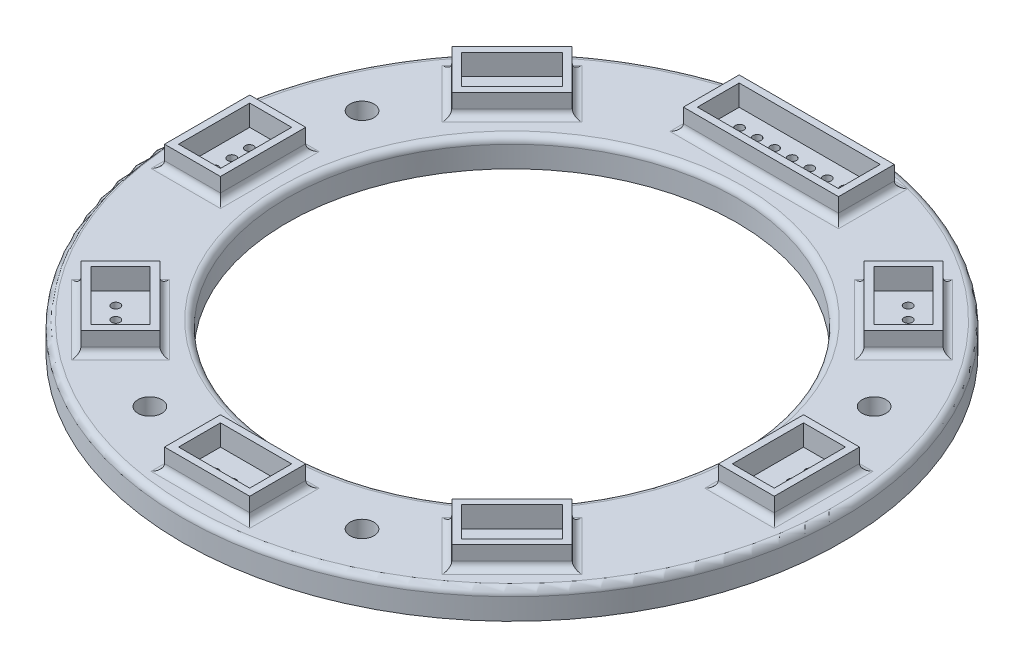
SolidWorks part; units mm, degrees
ref_plane "Front Plane" through (0, 0, 0) normal (0, 0, 1) x (1, 0, 0)
ref_plane "Top Plane" through (0, 0, 0) normal (0, 1, 0) x (1, 0, 0)
ref_plane "Right Plane" through (0, 0, 0) normal (1, 0, 0) x (0, 0, -1)
sketch "Sketch1" plane through (0, 0, 0) normal (0, 1, 0) x (1, 0, 0)
  circle A0 centre (0, 0) radius 32.05
  circle A1 centre (0, 0) radius 47
  dimension "D1" = 64.1
  dimension "D2" = 94
extrude "Boss-Extrude1" add sketch "Sketch1" along normal blind 1
sketch "Sketch2" plane through (0, 0, 0) normal (0, -1, 0) x (1, 0, 0)
  circle A0 centre (0, 0) radius 33.05
  circle A1 centre (0, 0) radius 46
  circle A2 centre (0, 0) radius 32.05 construction
  circle A3 centre (0, 0) radius 47 construction
  circle A4 centre (0, 0) radius 32.05
  circle A5 centre (0, 0) radius 47
  circle M4 centre (0, 0) radius 47
  circle M5 centre (0, 0) radius 32.05
  dimension "D1" = 1
  dimension "D2" = 1
extrude "Boss-Extrude2" add sketch "Sketch2" along normal blind 3 contours A1 M4 | A0 M5 region at (-32.1152, 0, 0) region at (-46.8671, 0, 0)
sketch "Sketch4" plane through (0, 1, 0) normal (0, 1, 0) x (1, 0, 0)
  line L0 (33.485, 26.4493) -> (26.4493, 33.485)
  line L1 (26.4493, 33.485) -> (22.3623, 29.398)
  line L2 (22.3623, 29.398) -> (29.398, 22.3623)
  line L3 (29.398, 22.3623) -> (33.485, 26.4493)
  line L4 (33.6265, 26.4493) -> (26.4493, 33.6265)
  line L5 (26.4493, 33.6265) -> (22.2208, 29.398)
  line L6 (22.2208, 29.398) -> (29.398, 22.2208)
  line L7 (29.398, 22.2208) -> (33.6265, 26.4493)
  line L8 (26.4493, 35.0407) -> (20.8066, 29.398)
  line L9 (20.8066, 29.398) -> (29.398, 20.8066)
  line L10 (29.398, 20.8066) -> (35.0407, 26.4493)
  line L11 (35.0407, 26.4493) -> (26.4493, 35.0407)
  line L12 (0, 0) -> (25.1023, 25.1023) construction
  line L13 (0, 0) -> (0, 27.9664) construction
  dimension "D3" = 36.6
  dimension "D4" = 9.95
  dimension "D5" = 5.78
  dimension "D6" = 45
  dimension "D1" = 0.1
  dimension "D2" = 1
extrude "Boss-Extrude3" add sketch "Sketch4" along normal blind 3 contours L10 L11 L8 L9 L7 L6 L5 L4 region at (30.6027, 1, -30.6027)
sketch "Sketch7" plane through (0, 1, 0) normal (0, 1, 0) x (1, 0, 0)
  line L0 (-30.4712, 26.4831) -> (-29.5661, 26.4831) construction
  line L1 (-28.7034, 28.2509) -> (-27.7983, 28.2509) construction
  line L2 (-26.9357, 30.0187) -> (-26.0306, 30.0187) construction
  circle A0 centre (-30.0187, 26.4831) radius 0.6
  circle A1 centre (-28.2509, 28.2509) radius 0.6
  circle A2 centre (-26.4831, 30.0187) radius 0.6
  dimension "D1" = 1.2
extrude "Cut-Extrude2" cut sketch "Sketch7" against normal up to next
pattern_circular "CirPattern4" count 8 over 360 about axis through (0, 1, 0) along (0, -1, 0) skipping 7 of "Boss-Extrude3"
sketch "Sketch5" plane through (0, 1, 0) normal (0, 1, 0) x (1, 0, 0)
  line L25 (-10.06, 36.5) -> (-10.06, 42.46)
  line L26 (-9.96, 36.6) -> (9.96, 36.6)
  line L27 (-9.96, 36.6) -> (-9.96, 42.36)
  line L28 (-9.96, 42.36) -> (9.96, 42.36)
  line L29 (9.96, 36.6) -> (9.96, 42.36)
  line L30 (-10.06, 42.46) -> (10.06, 42.46)
  line L31 (10.06, 36.5) -> (10.06, 42.46)
  line L32 (-10.06, 36.5) -> (10.06, 36.5)
  line L33 (-11.06, 35.5) -> (11.06, 35.5)
  line L34 (11.06, 35.5) -> (11.06, 43.46)
  line L35 (-11.06, 43.46) -> (11.06, 43.46)
  line L36 (-11.06, 35.5) -> (-11.06, 43.46)
  point P0 (0, 43.46)
  dimension "D1" = 36.6
  dimension "D2" = 5.76
  dimension "D5" = 19.92
  dimension "D3" = 0.1
  dimension "D4" = 1
extrude "Boss-Extrude4" add sketch "Sketch5" along normal blind 3 contours L36 L33 L34 L35 L32 L25 L30 L31 region at (-10.8249, 1, -39.48)
fillet "Fillet2" radius 0.96 34 edges at (-32.2193, 1, -23.628) (-25.1023, 1, -25.1023) (-23.628, 1, -32.2193) (-30.745, 1, -30.745) (-39.49, 1, 6.075) (-35.5, 1, 0) (-39.49, 1, -6.075) (-43.48, 1, 0) (-23.628, 1, 32.2193) (-25.1023, 1, 25.1023) (-32.2193, 1, 23.628) (-30.745, 1, 30.745) (6.075, 1, 39.49) (0, 1, 35.5) (-6.075, 1, 39.49) (0, 1, 43.48) (32.2193, 1, 23.628) (25.1023, 1, 25.1023) (23.628, 1, 32.2193) (30.745, 1, 30.745) (23.628, 1, -32.2193) (25.1023, 1, -25.1023) (32.2193, 1, -23.628) (30.745, 1, -30.745) (0, 1, 32.05) (0, 1, 47) (39.49, 1, -6.075) (35.5, 1, 0) (39.49, 1, 6.075) (43.48, 1, 0) (0, 1, -35.5) (11.06, 1, -39.48) (0, 1, -43.46) (-11.06, 1, -39.48)
pattern_circular "CirPattern5" count 8 over 360 about axis through (0, -3, 0) along (0, -1, 0) skipping 1 of "Cut-Extrude2"
sketch "Sketch9" plane through (0, 0, 0) normal (0, -1, 0) x (1, 0, 0)
  line L0 (-12.6477, 30.5342) -> (-17.6034, 42.4985) construction
  line L1 (-30.5342, -12.6477) -> (-42.4985, -17.6034) construction
  line L2 (0, 0) -> (-30.5342, -12.6477) construction
  line L3 (-12.6477, 30.5342) -> (0, 0) construction
  line L4 (0, -16.5006) -> (0, 16.5006) construction
  circle A0 centre (-36.5163, -15.1256) radius 3
  circle A1 centre (-15.1256, 36.5163) radius 3
  circle A2 centre (0, 0) radius 33.05 construction
  circle A3 centre (0, 0) radius 46 construction
  circle A4 centre (0, 0) radius 46 construction
  dimension "D3" = 6
  dimension "D1" = 22.5
  dimension "D2" = 67.5
extrude "Boss-Extrude5" add sketch "Sketch9" along normal up to surface (3 mm away) up to face at (0, -3, -46)
hole_wizard "M3 Clearance Hole1" positions "Sketch10" profile "Sketch11" hole size "M3" standard "ISO" end condition through all
sketch "Sketch10" plane through (0, 1, 0) normal (0, 1, 0) x (1, 0, 0)
  point P0 (-15.1256, -36.5163)
  point P2 (-36.5163, 15.1256)
sketch "Sketch11" plane through (-15.1256, 1, 36.5163) normal (1, 0, 0) x (0, 0, 1)
  line L0 (0, 0) -> (0, 4)
  line L1 (0, 4) -> (1.7, 4)
  line L2 (1.7, 4) -> (1.7, 0)
  line L5 (1.7, 0) -> (0, 0)
  line L11 (0, -6.35) -> (0, 107.95) construction
  dimension "Thru Hole Dia." = 3.4
  dimension "Thru Hole Depth" = 4
fillet "Fillet3" radius 1.5 2 edges at (-15.1256, 0, 39.5163) (-36.5163, 0, -12.1256)
mirror "Mirror1" about plane through (0, 0, 0) normal (1, 0, 0) of "Boss-Extrude5", "M3 Clearance Hole1", "Fillet3"
sketch "Sketch12" plane through (0, 1, 0) normal (0, 1, 0) x (1, 0, 0)
  line L0 (-7.82, 39.6328) -> (-7.18, 40.2728) construction
  line L1 (7.18, 39.6328) -> (7.82, 40.2728) construction
  circle A0 centre (-7.5, 39.9528) radius 0.6
  circle A1 centre (-5, 39.9528) radius 0.6
  circle A2 centre (-2.5, 39.9528) radius 0.6
  circle A3 centre (0, 39.9528) radius 0.6
  circle A4 centre (2.5, 39.9528) radius 0.6
  circle A5 centre (5, 39.9528) radius 0.6
  circle A6 centre (7.5, 39.9528) radius 0.6
  dimension "D1" = 1.2
  dimension "D2" = 7
extrude "Cut-Extrude3" cut sketch "Sketch12" against normal up to next
